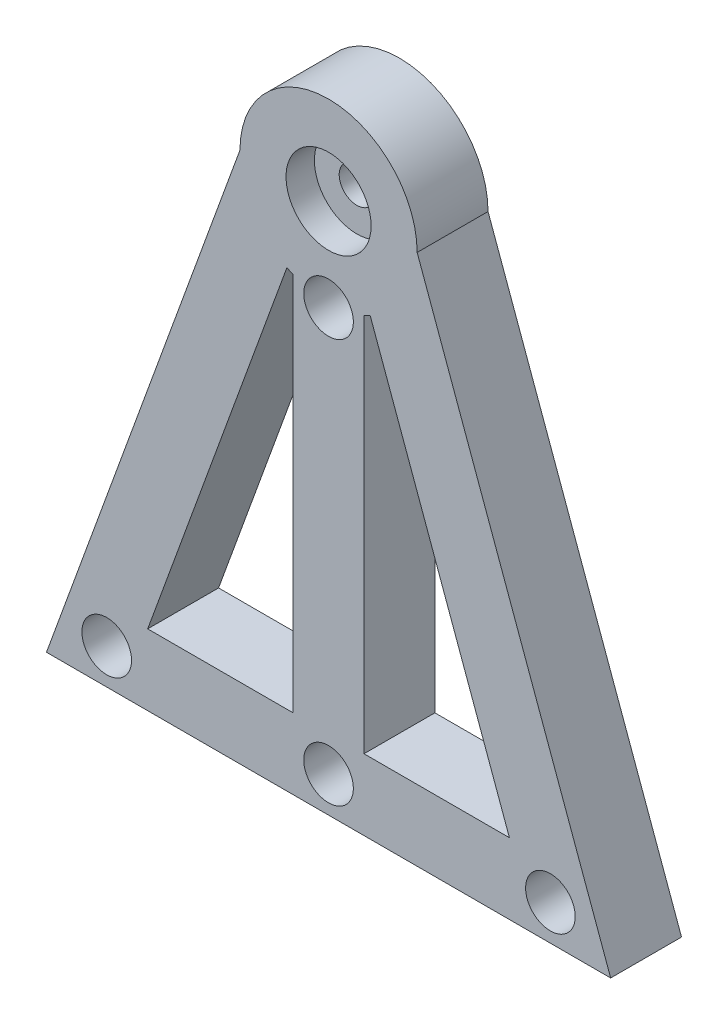
SolidWorks part; units mm, degrees
ref_plane "Front Plane" through (0, 0, 0) normal (0, 0, 1) x (1, 0, 0)
ref_plane "Top Plane" through (0, 0, 0) normal (0, 1, 0) x (1, 0, 0)
ref_plane "Right Plane" through (0, 0, 0) normal (1, 0, 0) x (0, 0, -1)
sketch "Sketch1" plane through (0, 0, 0) normal (0, 0, 1) x (1, 0, 0)
  line L0 (0, 0) -> (0, 75)
  line L1 (-39.7978, 0) -> (39.7978, 0)
  line L2 (-12.5, 75) -> (-39.7978, 0)
  line L3 (12.5, 75) -> (39.7978, 0)
  line L4 (0, 0) -> (0, 10)
  line L5 (-5.8742, 63.9662) -> (-25.5163, 10)
  line L6 (-25.5163, 10) -> (25.5163, 10)
  line L7 (5.8742, 63.9662) -> (25.5163, 10)
  line L8 (-3.1031, 71.5798) -> (-25.5163, 10) construction
  line L9 (3.1031, 71.5798) -> (25.5163, 10) construction
  line L10 (-5, 10) -> (5, 10)
  line L11 (-5, 10) -> (-5, 63.5436)
  line L12 (5, 10) -> (5, 63.5436)
  line L14 (-12.5, 75) -> (-39.7978, 0) construction
  circle A2 centre (0, 75) radius 12.5
  arc A3 (12.5, 75) -> (5.8742, 63.9662) centre (0, 75) cw
  arc A4 (-5.8742, 63.9662) -> (-12.5, 75) centre (0, 75) cw
  arc A5 (-5, 63.5436) -> (5, 63.5436) centre (0, 75) ccw
  point P8 (0, 0)
  point P21 (0, 10)
  dimension "D2" = 25
  dimension "D1" = 75
  dimension "D3" = 70
  dimension "D4" = 10
  dimension "D6" = 10
  dimension "D5" = 10
extrude "Boss-Extrude1" add sketch "Sketch1" along normal blind 10 contours A2 | A4 L2 L1 L3 A3 L7 L6 L5 | L11 A5 L12 L10
sketch "Sketch2" plane through (0, 0, 10) normal (0, 0, 1) x (1, 0, 0)
  arc A0 (12.5, 75) -> (-12.5, 75) centre (0, 75) ccw construction
  arc A1 (12.5, 75) -> (-12.5, 75) centre (0, 75) ccw
  circle A2 centre (0, 75) radius 2.5
  circle A3 centre (0, 75) radius 6
  dimension "D1" = 5
  dimension "D2" = 12
extrude "Cut-Extrude1" cut sketch "Sketch2" against normal up to next contours A2
extrude "Cut-Extrude2" cut sketch "Sketch2<3>" against normal blind 4 contours A3 A2 region at (-5.8303, 75, 10)
sketch "Sketch2<3>" plane through (0, 0, 10) normal (0, 0, 1) x (1, 0, 0) same geometry as "Sketch2"
sketch "Sketch3" plane through (0, 0, 10) normal (0, 0, 1) x (1, 0, 0)
  line L0 (12.5, 75) -> (39.7978, 0) construction
  line L1 (5.8742, 63.9662) -> (25.5163, 10) construction
  line L2 (5, 10) -> (25.5163, 10) construction
  line L3 (5, 10) -> (5, 63.5436) construction
  line L4 (-5, 10) -> (-5, 63.5436) construction
  line L5 (-5.8742, 63.9662) -> (-25.5163, 10) construction
  line L6 (-25.5163, 10) -> (-5, 10) construction
  line L7 (-12.5, 75) -> (-39.7978, 0) construction
  line L8 (-39.7978, 0) -> (39.7978, 0) construction
  line L9 (12.5, 75) -> (39.7978, 0) construction
  line L10 (5.8742, 63.9662) -> (25.5163, 10) construction
  line L11 (5, 10) -> (25.5163, 10) construction
  line L12 (5, 10) -> (5, 63.5436) construction
  line L13 (-5, 10) -> (-5, 63.5436) construction
  line L14 (-5.8742, 63.9662) -> (-25.5163, 10) construction
  line L15 (-25.5163, 10) -> (-5, 10) construction
  line L16 (-12.5, 75) -> (-39.7978, 0) construction
  line L17 (-39.7978, 0) -> (39.7978, 0) construction
  line L18 (-39.7978, 0) -> (-39.7978, 5) construction
  line L19 (39.7978, 0) -> (39.7978, 5) construction
  line L20 (-39.7978, 5) -> (39.7978, 5) construction
  line L21 (-39.7978, 5) -> (-31.2978, 5) construction
  line L22 (39.7978, 5) -> (31.2978, 5) construction
  line L23 (0, 75) -> (0, 5) construction
  line L24 (0, 75) -> (0, 62) construction
  arc A0 (5, 63.5436) -> (5.8742, 63.9662) centre (0, 75) ccw construction
  arc A1 (-5.8742, 63.9662) -> (-5, 63.5436) centre (0, 75) ccw construction
  circle A2 centre (0, 75) radius 6 construction
  arc A3 (12.5, 75) -> (-12.5, 75) centre (0, 75) ccw construction
  arc A4 (5, 63.5436) -> (5.8742, 63.9662) centre (0, 75) ccw construction
  arc A5 (-5.8742, 63.9662) -> (-5, 63.5436) centre (0, 75) ccw construction
  circle A6 centre (0, 75) radius 6 construction
  arc A7 (12.5, 75) -> (-12.5, 75) centre (0, 75) ccw construction
  circle A8 centre (0, 5) radius 1.5
  circle A9 centre (31.2978, 5) radius 1.5
  circle A10 centre (-31.2978, 5) radius 1.5
  circle A11 centre (0, 62) radius 1.5
  circle A12 centre (-31.2978, 5) radius 3.5
  circle A13 centre (0, 5) radius 3.5
  circle A14 centre (31.2978, 5) radius 3.5
  circle A15 centre (0, 62) radius 3.5
  dimension "D6" = 3
  dimension "D7" = 3
  dimension "D8" = 3
  dimension "D9" = 3
  dimension "D10" = 7
  dimension "D11" = 7
  dimension "D12" = 7
  dimension "D13" = 7
  dimension "D1" = 5
  dimension "D2" = 5
  dimension "D3" = 8.5
  dimension "D4" = 8.5
  dimension "D5" = 13
extrude "Cut-Extrude4" cut sketch "Sketch3" against normal up to next contours A10 | A8 | A9 | A11 region at (0, 5, 10) region at (31.2978, 5, 10) region at (-31.2978, 5, 10)
extrude "Cut-Extrude5" cut sketch "Sketch3<4>" against normal blind 5 contours A12 A10 | A13 A8 | A14 A9 | A15 region at (-34.6988, 5, 10) region at (-3.401, 5, 10) region at (27.8968, 5, 10)
sketch "Sketch3<4>" plane through (0, 0, 10) normal (0, 0, 1) x (1, 0, 0) same geometry as "Sketch3"
